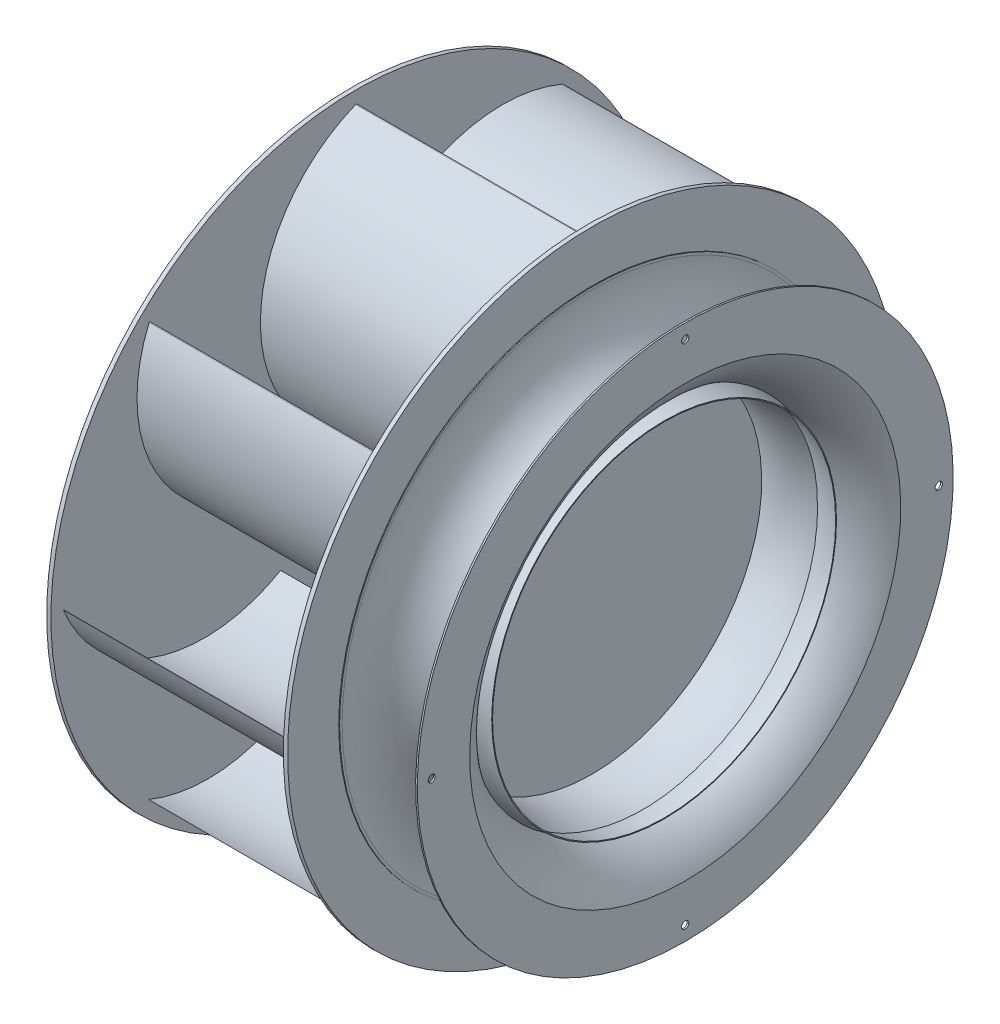
SolidWorks part; units mm, degrees
note: '?' marks a value the reader was unsure of.
ref_plane "Front Plane" through (0, 0, 0) normal (0, 0, 1) x (1, 0, 0)
ref_plane "Top Plane" through (0, 0, 0) normal (0, 1, 0) x (1, 0, 0)
ref_plane "Right Plane" through (0, 0, 0) normal (1, 0, 0) x (0, 0, -1)
sketch "Sketch1" plane through (0, 0, 0) normal (0, 0, 1) x (1, 0, 0)
  line L0 (0, 0) -> (831.9083, 0) construction
  line L1 (0, 0) -> (0, 109)
  line L2 (5, 114) -> (70, 114)
  line L3 (70, 114) -> (70, 138)
  line L4 (70, 138) -> (90, 138)
  line L5 (90, 138) -> (90, 98)
  line L6 (90, 98) -> (92, 98)
  line L7 (92, 98) -> (92, 133)
  line L8 (92, 133) -> (95, 133)
  line L9 (95, 133) -> (95, 98)
  line L10 (95, 98) -> (97, 98)
  line L11 (97, 98) -> (97, 0)
  line L12 (97, 0) -> (0, 0)
  arc A0 (5, 114) -> (0, 109) centre (5, 109) ccw
  point P16 (0, 114)
  dimension "D10" = 5
  dimension "D1" = 114
  dimension "D2" = 24
  dimension "D3" = 70
  dimension "D4" = 40
  dimension "D5" = 35
  dimension "D6" = 2
  dimension "D7" = 20
  dimension "D8" = 3
  dimension "D9" = 27
revolve "Revolve1" add sketch "Sketch1" angle 360 about L0
sketch "Sketch2" plane through (97, 0, 0) normal (1, 0, 0) x (0, 0, -1)
  circle A0 centre (0, 0) radius 360.5
  dimension "D1" = 721
extrude "Extrude1" add sketch "Sketch2" along normal blind 5
sketch "Sketch9" plane through (97, 0, 0) normal (-1, 0, 0) x (0, 0, 1)
  circle A0 centre (0, 0) radius 355.5
  circle A1 centre (0, 0) radius 100
  circle A2 centre (0, 0) radius 360.5 construction
  dimension "D1" = 5
  dimension "D2" = 200
extrude "Extrude7" cut sketch "Sketch9" against normal blind 3
ref_plane "Plane1" through (377, 0, 0) normal (1, 0, 0) x (0, 0, -1)
sketch "Sketch3" plane through (377, 0, 0) normal (1, 0, 0) x (0, 0, -1)
  circle A0 centre (0, 0) radius 360.5
  dimension "D1" = 721
extrude "Extrude2" add sketch "Sketch3" along normal blind 5 separate body
sketch "Sketch4" plane through (102, 0, 0) normal (1, 0, 0) x (0, 0, -1)
  line L0 (0, 0) -> (0, 345.5) construction
  line L1 (0, 0) -> (254.912, 254.912) construction
  line L2 (0, 125) -> (0.866, 124.5)
  line L3 (244.3054, 244.3054) -> (245.1714, 243.8054)
  circle A0 centre (0, 0) radius 345.5 construction
  circle A1 centre (0, 0) radius 360.5 construction
  circle A2 centre (0, 0) radius 125 construction
  arc A3 (0, 125) -> (244.3054, 244.3054) centre (173.926, 78.6348) cw
  arc A4 (0.866, 124.5) -> (245.1714, 243.8054) centre (174.7921, 78.1348) cw
  dimension "D1" = 15
  dimension "D2" = 250
  dimension "D6" = 180
  dimension "D7" = 180
  dimension "D3" = 45
  dimension "D4" = 60
  dimension "D5" = 1
extrude "Extrude3" add sketch "Sketch4" along normal up to surface (280 mm away) up to face at (382, 0, -360.5)
ref_axis "Axis1" through (253.5503, 0, 0) along (-1, 0, 0)?
pattern_circular "CirPattern1" count 8 over 360 about axis through (0, 0, 0) along (1, 0, 0) of "Extrude3"
sketch "Sketch5" plane through (0, 0, 0) normal (0, 0, 1) x (1, 0, 0)
  line L0 (0, 0) -> (527.2916, 0) construction
  line L1 (253.5503, 0) -> (75.411, 0) construction
  line L2 (382, 300) -> (383, 300)
  line L3 (383, 300) -> (383, 297)
  line L4 (382, 300) -> (382, 297)
  line L5 (467, 204) -> (467, 203)
  line L6 (70, 138) -> (70, -138) construction
  line L7 (382, -360.5) -> (382, 360.5) construction
  arc A0 (383, 297) -> (467, 204) centre (467.6225, 288.9977) ccw
  arc A1 (382, 297) -> (467, 203) centre (466.522, 287.9987) ccw
  dimension "D7" = 85
  dimension "D8" = 85
  dimension "D1" = 203
  dimension "D2" = 1
  dimension "D3" = 1
  dimension "D4" = 3
  dimension "D5" = 300
  dimension "D6" = 397
revolve "Revolve2" add sketch "Sketch5" angle 360 about L0
ref_plane "Plane3" through (492, 0, 0) normal (1, 0, 0) x (0, 0, -1)
sketch "Sketch6" plane through (0, 0, 0) normal (0, 0, 1) x (1, 0, 0)
  line L0 (492, 317) -> (490, 317)
  line L1 (492, -251.35) -> (492, 251.35) construction
  line L2 (490, 317) -> (490, 255)
  line L3 (0, 0) -> (615.1417, 0) construction
  line L4 (0, 114) -> (0, -114) construction
  line L5 (253.5503, 0) -> (75.411, 0) construction
  line L6 (492, 317) -> (492, 255)
  line L7 (375, 203) -> (379, 203)
  line L8 (375, 203) -> (375, 201)
  line L9 (375, 201) -> (379, 201)
  arc A0 (379, 203) -> (490, 255) centre (400.9789, 300.5548) ccw
  arc A1 (379, 201) -> (492, 255) centre (401.883, 298.3466) ccw
  dimension "D7" = 100
  dimension "D8" = 100
  dimension "D1" = 317
  dimension "D2" = 2
  dimension "D3" = 255
  dimension "D4" = 117
  dimension "D5" = 203
  dimension "D6" = 4
revolve "Revolve3" add sketch "Sketch6" angle 360 about L3
sketch "Sketch7" plane through (492, 0, 0) normal (1, 0, 0) x (0, 0, -1)
  line L0 (0, 0) -> (0, 300) construction
  circle A0 centre (0, 0) radius 300 construction
  circle A1 centre (0, 300) radius 4.25
  dimension "D1" = 600
  dimension "D2" = 8.5
extrude "Extrude5" cut sketch "Sketch7" against normal blind 5
pattern_circular "CirPattern2" count 4 over 360 about axis through (0, 0, 0) along (1, 0, 0) of "Extrude5"
sketch "Sketch8" plane through (0, 0, 0) normal (1, 0, 0) x (0, 0, -1)
  line L0 (0, 0) -> (0, 126) construction
  circle A0 centre (0, 0) radius 126 construction
  circle A1 centre (0, 126) radius 5
  dimension "D1" = 252
  dimension "D2" = 10
extrude "Extrude6" cut sketch "Sketch8" along normal up to surface (90 mm away) up to face at (90, 0, 138)
pattern_circular "CirPattern3" count 8 over 360 about axis through (0, 0, 0) along (1, 0, 0) of "Extrude6"
